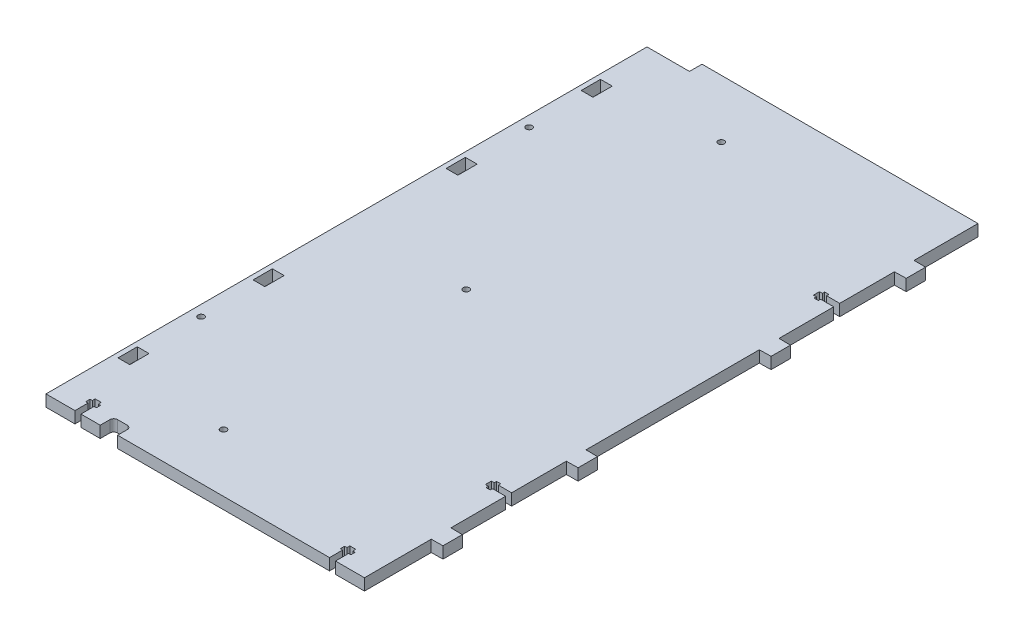
SolidWorks part; units mm, degrees
material "Клен"
ref_plane "Front" through (0, 0, 0) normal (0, 0, 1) x (1, 0, 0)
ref_plane "Top" through (0, 0, 0) normal (0, 1, 0) x (1, 0, 0)
ref_plane "Right" through (0, 0, 0) normal (1, 0, 0) x (0, 0, -1)
sketch "Эскиз1" plane through (0, 0, 6) normal (0, 1, 0) x (1, 0, 0)
  line L0 (830.1555, 858.9465) -> (830.1555, 507.3335) construction
  line L1 (746.0135, 673.4222) -> (945.6578, 673.4222) construction
  line L2 (746.0135, 805.6234) -> (945.6578, 805.6234) construction
  line L3 (746.0135, 547.7211) -> (945.6578, 547.7211) construction
  line L16 (776.7555, 552.5234) -> (776.7555, 562.5234)
  line L17 (770.6555, 562.5234) -> (770.6555, 552.5234)
  line L18 (770.6555, 552.5234) -> (776.7555, 552.5234)
  line L19 (776.7555, 562.5234) -> (770.6555, 562.5234)
  line L20 (770.6555, 622.5234) -> (776.7555, 622.5234)
  line L21 (776.7555, 622.5234) -> (776.7555, 632.5234)
  line L22 (776.7555, 632.5234) -> (770.6555, 632.5234)
  line L23 (770.6555, 632.5234) -> (770.6555, 622.5234)
  line L24 (776.7555, 722.5234) -> (776.7555, 732.5234)
  line L25 (770.6555, 722.5234) -> (776.7555, 722.5234)
  line L26 (770.6555, 732.5234) -> (770.6555, 722.5234)
  line L27 (776.7555, 732.5234) -> (770.6555, 732.5234)
  line L28 (770.6555, 792.5234) -> (776.7555, 792.5234)
  line L29 (776.7555, 792.5234) -> (776.7555, 802.5234)
  line L30 (776.7555, 802.5234) -> (770.6555, 802.5234)
  line L31 (770.6555, 802.5234) -> (770.6555, 792.5234)
  line L32 (833.1555, 858.9465) -> (833.1555, 507.3335) construction
  line L33 (933.1555, 858.9465) -> (933.1555, 507.3335) construction
  line L34 (933.1555, 517.7211) -> (933.1555, 552.3234)
  line L35 (933.1555, 593.9734) -> (933.1555, 622.3234)
  line L36 (933.1555, 622.3234) -> (939.1555, 622.4234)
  line L37 (924.1555, 589.6734) -> (924.1555, 590.8734)
  line L38 (939.1555, 722.4234) -> (939.1555, 732.4234)
  line L39 (939.1555, 562.4234) -> (933.1555, 562.5234)
  line L40 (924.1555, 765.1734) -> (926.3555, 765.1734)
  line L41 (933.1555, 562.5234) -> (933.1555, 590.8734)
  line L42 (926.3555, 589.6734) -> (924.1555, 589.6734)
  line L43 (922.6555, 760.8734) -> (922.6555, 763.9734)
  line L44 (926.3555, 759.6734) -> (924.1555, 759.6734)
  line L45 (933.1555, 763.9734) -> (933.1555, 792.3234)
  line L46 (926.3555, 595.1734) -> (926.3555, 593.9734)
  line L47 (926.3555, 760.8734) -> (926.3555, 759.6734)
  line L48 (939.1555, 622.4234) -> (939.1555, 632.4234)
  line L49 (939.1555, 732.4234) -> (933.1555, 732.5234)
  line L50 (926.3555, 763.9734) -> (933.1555, 763.9734)
  line L51 (926.3555, 593.9734) -> (933.1555, 593.9734)
  line L52 (924.1555, 760.8734) -> (922.6555, 760.8734)
  line L53 (933.1555, 590.8734) -> (926.3555, 590.8734)
  line L54 (933.1555, 632.5234) -> (933.1555, 722.3234)
  line L55 (924.1555, 763.9734) -> (924.1555, 765.1734)
  line L56 (933.1555, 802.5234) -> (933.1555, 835.6234)
  line L57 (924.1555, 590.8734) -> (922.6555, 590.8734)
  line L58 (924.1555, 595.1734) -> (926.3555, 595.1734)
  line L59 (933.1555, 792.3234) -> (939.1555, 792.4234)
  line L60 (933.1555, 760.8734) -> (926.3555, 760.8734)
  line L61 (922.6555, 763.9734) -> (924.1555, 763.9734)
  line L124 (805.2555, 522.7211) -> (805.2555, 517.7211)
  line L125 (805.2555, 517.7211) -> (833.1555, 517.7211)
  line L167 (833.1555, 835.6234) -> (790.1555, 835.6234)
  line L168 (790.1555, 835.6234) -> (790.1555, 829.1234)
  line L169 (790.1555, 829.1234) -> (768.1555, 829.1234)
  line L170 (768.1555, 829.1234) -> (768.1555, 517.7211)
  line L171 (768.1555, 517.7211) -> (783.1555, 517.7211)
  line L172 (783.1555, 517.7211) -> (783.1555, 524.5211)
  line L173 (783.1555, 524.5211) -> (781.9555, 524.5211)
  line L174 (781.9555, 524.5211) -> (781.9555, 526.7211)
  line L175 (781.9555, 526.7211) -> (783.1555, 526.7211)
  line L176 (783.1555, 526.7211) -> (783.1555, 528.2211)
  line L177 (783.1555, 528.2211) -> (786.2555, 528.2211)
  line L178 (786.2555, 528.2211) -> (786.2555, 526.7211)
  line L179 (786.2555, 526.7211) -> (787.4555, 526.7211)
  line L180 (787.4555, 526.7211) -> (787.4555, 524.5211)
  line L181 (787.4555, 524.5211) -> (786.2555, 524.5211)
  line L182 (786.2555, 524.5211) -> (786.2555, 517.7211)
  line L183 (786.2555, 517.7211) -> (796.2555, 517.7211)
  line L184 (796.2555, 517.7211) -> (796.2555, 522.7211)
  line L185 (798.2555, 524.7211) -> (803.2555, 524.7211)
  line L186 (926.3555, 590.8734) -> (926.3555, 589.6734)
  line L187 (939.1555, 632.4234) -> (933.1555, 632.5234)
  line L188 (933.1555, 552.3234) -> (939.1555, 552.4234)
  line L189 (922.6555, 590.8734) -> (922.6555, 593.9734)
  line L190 (933.1555, 722.3234) -> (939.1555, 722.4234)
  line L191 (933.1555, 732.5234) -> (933.1555, 760.8734)
  line L192 (924.1555, 593.9734) -> (924.1555, 595.1734)
  line L193 (924.1555, 759.6734) -> (924.1555, 760.8734)
  line L194 (926.3555, 765.1734) -> (926.3555, 763.9734)
  line L195 (939.1555, 802.4234) -> (933.1555, 802.5234)
  line L196 (939.1555, 552.4234) -> (939.1555, 562.4234)
  line L197 (922.6555, 593.9734) -> (924.1555, 593.9734)
  line L198 (939.1555, 792.4234) -> (939.1555, 802.4234)
  line L199 (833.1555, 835.6234) -> (933.1555, 835.6234)
  line L200 (933.1555, 517.7211) -> (918.1555, 517.7211)
  line L201 (915.0555, 517.7211) -> (915.0555, 524.5211)
  line L202 (913.8555, 526.7211) -> (915.0555, 526.7211)
  line L203 (919.3555, 524.5211) -> (918.1555, 524.5211)
  line L204 (915.0555, 524.5211) -> (913.8555, 524.5211)
  line L205 (918.1555, 526.7211) -> (919.3555, 526.7211)
  line L206 (918.1555, 524.5211) -> (918.1555, 517.7211)
  line L207 (915.0555, 526.7211) -> (915.0555, 528.2211)
  line L208 (913.8555, 524.5211) -> (913.8555, 526.7211)
  line L209 (918.1555, 528.2211) -> (918.1555, 526.7211)
  line L210 (915.0555, 528.2211) -> (918.1555, 528.2211)
  line L211 (919.3555, 526.7211) -> (919.3555, 524.5211)
  line L212 (915.0555, 517.7211) -> (833.1555, 517.7211)
  circle A0 centre (830.1555, 805.6234) radius 1.6
  circle A1 centre (830.1555, 673.4222) radius 1.6
  circle A2 centre (830.1555, 547.7211) radius 1.6
  arc A4 (805.2555, 522.7211) -> (803.2555, 524.7211) centre (803.2555, 522.7211) ccw
  arc A5 (798.2555, 524.7211) -> (796.2555, 522.7211) centre (798.2555, 522.7211) ccw
  circle A6 centre (773.7055, 592.5234) radius 1.6
  circle A7 centre (773.7055, 762.5234) radius 1.6
  dimension "D7" = 3.2
  dimension "D8" = 3.2
  dimension "D9" = 3.2
  dimension "D2" = 100
  dimension "D3" = 15
  dimension "D4" = 30
  dimension "D1" = 3
  dimension "D5" = 30
  dimension "D6" = 162.2012
extrude "Бобышка-Вытянуть1" add sketch "Эскиз1" against normal blind 6
